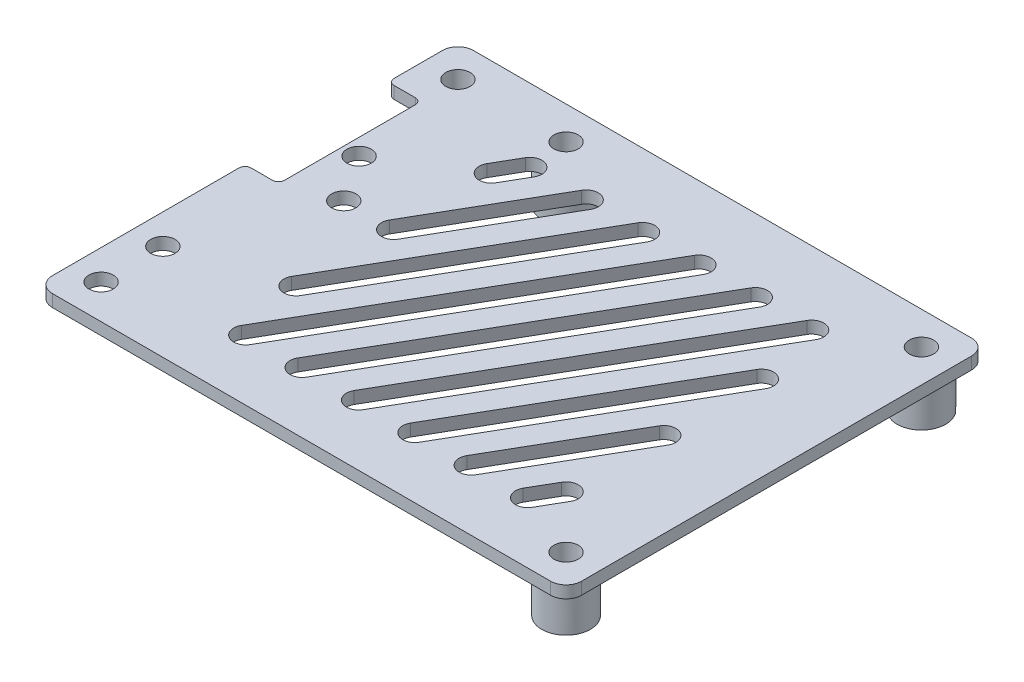
SolidWorks part; units mm, degrees
ref_plane "Front Plane" through (0, 0, 0) normal (0, 0, 1) x (1, 0, 0)
ref_plane "Top Plane" through (0, 0, 0) normal (0, 1, 0) x (1, 0, 0)
ref_plane "Right Plane" through (0, 0, 0) normal (1, 0, 0) x (0, 0, -1)
sketch "Sketch1" plane through (0, 0, 0) normal (0, 1, 0) x (1, 0, 0)
  line L0 (38.1, -29.21) -> (43.5, -34.61)
  line L1 (-38.1, -29.21) -> (38.1, -29.21) construction
  line L2 (-38.1, -29.21) -> (-38.1, 29.21) construction
  line L3 (-38.1, 29.21) -> (38.1, 29.21) construction
  line L4 (38.1, -29.21) -> (38.1, 29.21) construction
  line L5 (-38.1, -29.21) -> (38.1, 29.21) construction
  line L6 (-38.1, 29.21) -> (38.1, -29.21) construction
  line L7 (-43.5, -34.61) -> (43.5, -34.61)
  line L8 (-43.5, -34.61) -> (-43.5, 34.61)
  line L9 (-43.5, 34.61) -> (43.5, 34.61)
  line L10 (43.5, -34.61) -> (43.5, 34.61)
  line L11 (-43.5, -34.61) -> (43.5, 34.61) construction
  line L12 (-43.5, 34.61) -> (43.5, -34.61) construction
  circle A0 centre (-38.1, 29.21) radius 2
  circle A1 centre (38.1, 29.21) radius 2
  circle A2 centre (-20.32, 29.21) radius 2
  circle A3 centre (38.1, -29.21) radius 2
  point P0 (0, 0)
  point P11 (0, 0)
  dimension "D3" = 4
  dimension "D1" = 58.42
  dimension "D2" = 76.2
  dimension "D4" = 17.78
  dimension "D5" = 87
  dimension "D6" = 45
extrude "Boss-Extrude1" add sketch "Sketch1" along normal blind 2 contours A3 L10 L9 L8 L7 A2 A1 A0 region at (-0.0374, 0, 0.1229)
sketch "Sketch2" plane through (0, 0, 0) normal (0, -1, 0) x (1, 0, 0)
  circle A0 centre (38.1, -29.21) radius 4
  circle A1 centre (38.1, -29.21) radius 2
  circle A2 centre (38.1, -29.21) radius 2
  circle A3 centre (-38.1, -29.21) radius 2
  circle A4 centre (-38.1, -29.21) radius 2
  circle A5 centre (-20.32, -29.21) radius 2
  circle A6 centre (-20.32, -29.21) radius 2
  circle A7 centre (38.1, 29.21) radius 2
  circle A8 centre (38.1, 29.21) radius 2
  circle A9 centre (-20.32, -29.21) radius 4
  circle A10 centre (-38.1, -29.21) radius 4
  circle A11 centre (38.1, 29.21) radius 4
  dimension "D5" = 8
  dimension "D1" = 0
  dimension "D2" = 0
  dimension "D3" = 0
  dimension "D4" = 0
extrude "Boss-Extrude2" add sketch "Sketch2" along normal blind 7
sketch "Sketch3" plane through (0, 2, 0) normal (0, 1, 0) x (1, 0, 0)
  line L0 (-43.5, -34.61) -> (-43.5, 34.61) construction
  line L1 (-43.5, 23.11) -> (-38, 23.11)
  line L2 (-43.5, 23.11) -> (-43.5, -0.39)
  line L3 (-43.5, -0.39) -> (-38, -0.39)
  line L4 (-38, 23.11) -> (-38, -0.39)
  line L5 (-43.5, 34.61) -> (43.5, 34.61) construction
  line L6 (43.5, -34.61) -> (43.5, 34.61) construction
  line L7 (43.5, -21.11) -> (38, -21.11)
  line L8 (43.5, -21.11) -> (43.5, -12.61)
  line L9 (43.5, -12.61) -> (38, -12.61)
  line L10 (38, -21.11) -> (38, -12.61)
  line L11 (-43.5, -34.61) -> (43.5, -34.61) construction
  circle A0 centre (38.1, -29.21) radius 2 construction
  circle A1 centre (38.1, -29.21) radius 2
  line M5 (-43.5, 34.61) -> (-43.5, -34.61)
  dimension "D1" = 11.5
  dimension "D2" = 5.5
  dimension "D3" = 23.5
  dimension "D4" = 5.5
  dimension "D5" = 13.5
  dimension "D6" = 8.5
extrude "Cut-Extrude1" cut sketch "Sketch3" against normal blind 7 contours L4 L1 L3 M5 region at (-40.75, 2, -11.36)
sketch "Sketch4" plane through (0, 2, 0) normal (0, 1, 0) x (1, 0, 0)
  line L1 (-43.5, -34.61) -> (43.5, -34.61) construction
  line L2 (-38, -0.39) -> (-38, 23.11) construction
  line L3 (-38, 23.11) -> (-43.5, 23.11) construction
  line L4 (-43.5, -34.61) -> (-43.5, -0.39) construction
  circle A0 centre (-38.59, -28.97) radius 2
  circle A1 centre (-38.59, -18.81) radius 2
  circle A2 centre (-35.3, 10.16) radius 2
  dimension "D1" = 4
  dimension "D2" = 4.91
  dimension "D3" = 5.64
  dimension "D4" = 10.16
  dimension "D5" = 2.7
  dimension "D6" = 12.95
extrude "Cut-Extrude2" cut sketch "Sketch4" against normal blind 7
sketch "Sketch5" plane through (0, 2, 0) normal (0, 1, 0) x (1, 0, 0)
  line L0 (-22, 18.61) -> (-19.6906, 22.61) construction
  line L1 (-23.7321, 19.61) -> (-21.4226, 23.61)
  line L2 (-20.2679, 17.61) -> (-17.9585, 21.61)
  line L3 (-43.5, 34.61) -> (43.5, 34.61) construction
  line L4 (-22, 22.61) -> (29.5, 22.61) construction
  line L5 (-22, 22.61) -> (-22, -24.61) construction
  line L6 (-22, -24.61) -> (29.5, -24.61) construction
  line L7 (29.5, 22.61) -> (29.5, -24.61) construction
  line L8 (-43.5, -34.61) -> (43.5, -34.61) construction
  line L10 (-38, -0.39) -> (-38, 23.11) construction
  line L11 (-22, 2.5574) -> (-10.4226, 22.61) construction
  line L12 (-23.7321, 3.5574) -> (-12.1547, 23.61)
  line L13 (-20.2679, 1.5574) -> (-8.6906, 21.61)
  line L14 (-22, -13.4952) -> (-1.1547, 22.61) construction
  line L15 (-23.7321, -12.4952) -> (-2.8867, 23.61)
  line L16 (-20.2679, -14.4952) -> (0.5774, 21.61)
  line L17 (8.1133, 22.61) -> (-19.1492, -24.61) construction
  line L18 (9.8453, 21.61) -> (-17.4171, -25.61)
  line L19 (6.3812, 23.61) -> (-20.8813, -23.61)
  line L20 (-9.8812, -24.61) -> (17.3812, 22.61) construction
  line L21 (-11.6133, -23.61) -> (15.6492, 23.61)
  line L22 (-8.1492, -25.61) -> (19.1133, 21.61)
  line L23 (26.6492, 22.61) -> (-0.6133, -24.61) construction
  line L24 (28.3813, 21.61) -> (1.1188, -25.61)
  line L25 (24.9171, 23.61) -> (-2.3453, -23.61)
  line L26 (8.6547, -24.61) -> (29.5, 11.4952) construction
  line L27 (6.9226, -23.61) -> (27.7679, 12.4952)
  line L28 (10.3867, -25.61) -> (31.2321, 10.4952)
  line L29 (29.5, -4.5574) -> (17.9226, -24.61) construction
  line L30 (31.2321, -5.5574) -> (19.6547, -25.61)
  line L31 (27.7679, -3.5574) -> (16.1906, -23.61)
  line L32 (27.1906, -24.61) -> (29.5, -20.61) construction
  line L33 (25.4585, -23.61) -> (27.7679, -19.61)
  line L34 (28.9226, -25.61) -> (31.2321, -21.61)
  line L38 (-19.1132, 19.61) -> (-15.6264, 17.5969) construction
  line L39 (-14.4793, 11.5837) -> (-10.9924, 9.5706) construction
  line L40 (-9.8453, 3.5574) -> (-6.3584, 1.5443) construction
  line L41 (-3.7859, -2) -> (-0.299, -4.0131) construction
  line L42 (5.4821, -2) -> (8.9689, -4.0131) construction
  line L43 (14.75, -2) -> (18.2369, -4.0131) construction
  line L44 (20.8094, -7.5574) -> (24.2963, -9.5706) construction
  line L45 (25.4434, -15.5837) -> (28.9302, -17.5969) construction
  line L47 (43.5, -34.61) -> (43.5, 34.61) construction
  arc A0 (-23.7321, 19.61) -> (-20.2679, 17.61) centre (-22, 18.61) ccw
  arc A1 (-17.9585, 21.61) -> (-21.4226, 23.61) centre (-19.6906, 22.61) ccw
  arc A2 (-23.7321, 3.5574) -> (-20.2679, 1.5574) centre (-22, 2.5574) ccw
  arc A3 (-8.6906, 21.61) -> (-12.1547, 23.61) centre (-10.4226, 22.61) ccw
  arc A4 (-23.7321, -12.4952) -> (-20.2679, -14.4952) centre (-22, -13.4952) ccw
  arc A5 (0.5774, 21.61) -> (-2.8867, 23.61) centre (-1.1547, 22.61) ccw
  arc A6 (9.8453, 21.61) -> (6.3812, 23.61) centre (8.1133, 22.61) ccw
  arc A7 (-20.8813, -23.61) -> (-17.4171, -25.61) centre (-19.1492, -24.61) ccw
  arc A8 (-11.6133, -23.61) -> (-8.1492, -25.61) centre (-9.8812, -24.61) ccw
  arc A9 (19.1133, 21.61) -> (15.6492, 23.61) centre (17.3812, 22.61) ccw
  arc A10 (28.3813, 21.61) -> (24.9171, 23.61) centre (26.6492, 22.61) ccw
  arc A11 (-2.3453, -23.61) -> (1.1188, -25.61) centre (-0.6133, -24.61) ccw
  arc A12 (6.9226, -23.61) -> (10.3867, -25.61) centre (8.6547, -24.61) ccw
  arc A13 (31.2321, 10.4952) -> (27.7679, 12.4952) centre (29.5, 11.4952) ccw
  arc A14 (31.2321, -5.5574) -> (27.7679, -3.5574) centre (29.5, -4.5574) ccw
  arc A15 (16.1906, -23.61) -> (19.6547, -25.61) centre (17.9226, -24.61) ccw
  arc A16 (25.4585, -23.61) -> (28.9226, -25.61) centre (27.1906, -24.61) ccw
  arc A17 (31.2321, -21.61) -> (27.7679, -19.61) centre (29.5, -20.61) ccw
  point P2 (-20.8453, 20.61)
  point P11 (-16.2113, 12.5837)
  point P28 (-11.5773, 4.5574)
  point P35 (-5.518, -1)
  point P40 (3.75, -1)
  point P47 (13.018, -1)
  point P56 (19.0773, -6.5574)
  point P61 (23.7113, -14.5837)
  point P68 (28.3453, -22.61)
  dimension "D1" = 2
  dimension "D2" = 60
  dimension "D3" = 12
  dimension "D4" = 10
  dimension "D5" = 14
  dimension "D6" = 16
extrude "Cut-Extrude3" cut sketch "Sketch5" against normal blind 5
sketch "Sketch6" plane through (0, 2, 0) normal (0, 1, 0) x (1, 0, 0)
  line L1 (-43.5, -34.61) -> (43.5, -34.61) construction
  line L2 (-43.5, -34.61) -> (-43.5, -0.39) construction
  circle A0 centre (-30.2, 2.54) radius 2
  dimension "D1" = 4
  dimension "D2" = 13.3
  dimension "D3" = 37.15
extrude "Cut-Extrude4" cut sketch "Sketch6" against normal blind 10
fillet "Fillet1" radius 1 4 edges at (-38, 1, 0.39) (-43.5, 1, 0.39) (-38, 1, -23.11) (-43.5, 1, -23.11)
fillet "Fillet2" radius 2.54 4 edges at (43.5, 1, -34.61) (43.5, 1, 34.61) (-43.5, 1, 34.61) (-43.5, 1, -34.61)
